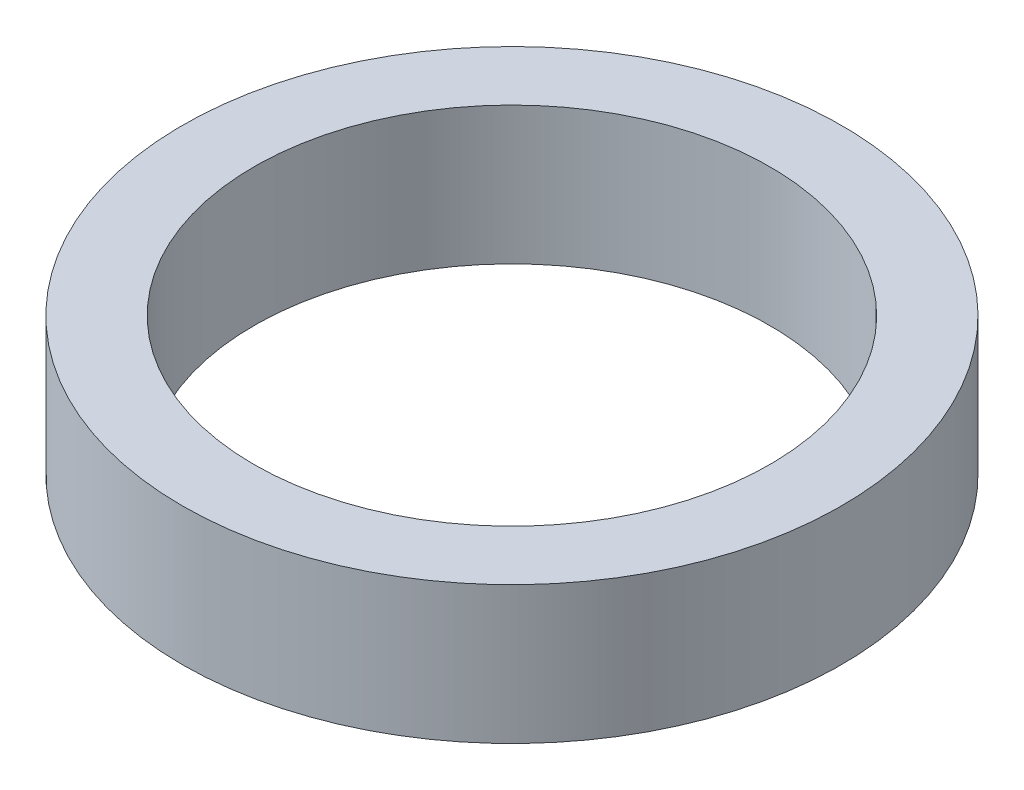
SolidWorks part; units mm, degrees
ref_plane "Front Plane" through (0, 0, 0) normal (0, 0, 1) x (1, 0, 0)
ref_plane "Top Plane" through (0, 0, 0) normal (0, 1, 0) x (1, 0, 0)
ref_plane "Right Plane" through (0, 0, 0) normal (1, 0, 0) x (0, 0, -1)
sketch "Sketch1" plane through (0, 0, 0) normal (0, 1, 0) x (1, 0, 0)
  circle A0 centre (0, 0) radius 57.5
  dimension "FLANGE_OD" = 115
extrude "Boss-Extrude1" add sketch "Sketch1" along normal blind 24
sketch "Sketch2" plane through (0, 0, 0) normal (0, 1, 0) x (1, 0, 0)
  circle A0 centre (0, 0) radius 45
  dimension "BORE_D" = 90
extrude "Cut-Extrude1" cut sketch "Sketch2" along normal through all
sketch "Sketch3" plane through (0, 24, 0) normal (0, 1, 0) x (1, 0, 0)
  circle A0 centre (0, 0) radius 24.214 construction
  circle A1 centre (-24.214, 0) radius 2.1772
  dimension "BOLT_D" = 4.3544
  dimension "BOLT_PCD" = 48.428
extrude "Cut-Extrude2" cut sketch "Sketch3" against normal blind 21.9632 rebuild error yes
pattern_circular "CirPattern1" count 8 over 360 rebuild error yes
